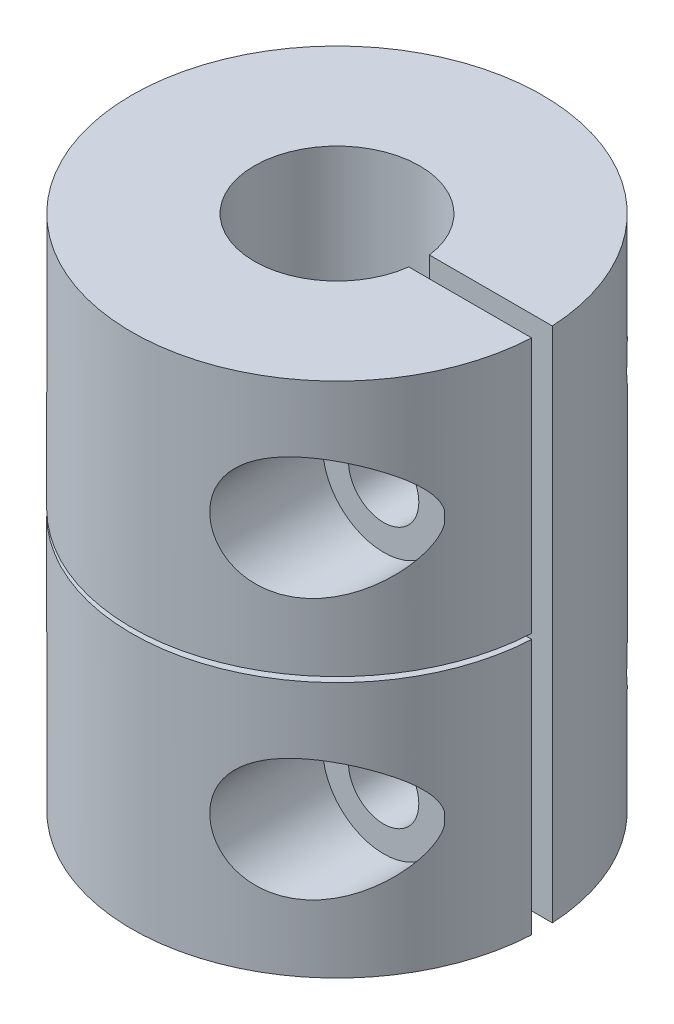
SolidWorks part; units mm, degrees
ref_plane "Front Plane" through (0, 0, 0) normal (0, 0, 1) x (1, 0, 0)
ref_plane "Top Plane" through (0, 0, 0) normal (0, 1, 0) x (1, 0, 0)
ref_plane "Right Plane" through (0, 0, 0) normal (1, 0, 0) x (0, 0, -1)
sketch "Sketch1" plane through (0, 0, 0) normal (0, 1, 0) x (1, 0, 0)
  circle A0 centre (0, 0) radius 9.925
  dimension "D1" = 19.85
extrude "Boss-Extrude1" add sketch "Sketch1" along normal mid plane 25
sketch "Sketch10" plane through (0, 0, 0) normal (0, 1, 0) x (1, 0, 0)
  line L0 (0, 0) -> (-4.9625, 8.5953)
  line L1 (0, 0) -> (9.925, 0) construction
  line L2 (0, -0.5) -> (9.9124, -0.5)
  line L3 (0, 0.5) -> (9.9124, 0.5)
  line L4 (0, 0.5) -> (9.925, 0.5) construction
  line L5 (0, -0.5) -> (9.925, -0.5) construction
  line L6 (0, -0.5) -> (0, 0)
  line L7 (0, 0.5) -> (-0.2887, 0.5)
  circle A0 centre (0, 0) radius 9.925 construction
  circle A2 centre (0, 0) radius 9.925
  circle A3 centre (0, 0) radius 9.925
  dimension "D1" = 60
  dimension "D2" = 0
  dimension "D3" = 0.5
  dimension "D4" = 0.5
extrude "Cut-Extrude5" cut sketch "Sketch10" against normal mid plane 0.25 contours L0 A3 L2 L6 region at (-1.5239, 0, 2.4216)
sketch "Sketch3" plane through (0, 12.5, 0) normal (0, 1, 0) x (1, 0, 0)
  circle A0 centre (0, 0) radius 4
  dimension "D1" = 8
extrude "Cut-Extrude1" cut sketch "Sketch3" against normal up to surface (12.625 mm away) up to face at (-0.6756, -0.125, 1.23)
sketch "Sketch4" plane through (0, -0.125, 0) normal (0, 1, 0) x (1, 0, 0)
  circle A0 centre (0, 0) radius 2.5
  dimension "D1" = 5
extrude "Cut-Extrude2" cut sketch "Sketch4" against normal through all
extrude "Cut-Extrude6" cut sketch "Sketch10<4>" against normal through all both and the other way through all contours L2 A3 L3 L7 L0 L6 region at (4.9239, 0, -0.0024)
sketch "Sketch10<4>" plane through (0, 0, 0) normal (0, 1, 0) x (1, 0, 0) same geometry as "Sketch10"
ref_plane "Plane1" through (0, 0, 9.925) normal (0, 0, 1) x (1, 0, 0)
hole_wizard "CBORE for M3 SHCS1" positions "Sketch11" profile "Sketch12" counterbore size "M3" standard "ANSI Metric" end condition up to next
sketch "Sketch11" plane through (0, 0, 9.925) normal (0, 0, 1) x (1, 0, 0)
  line L4 (6.1809, -12.5) -> (6.1809, -0.125) construction
  line L6 (2.4495, -12.5) -> (9.9124, -12.5) construction
  line L7 (2.4495, -0.125) -> (9.9124, -0.125) construction
  line L8 (0, 0) -> (9.9124, 0) construction
  line L9 (9.9124, -12.5) -> (9.9124, 12.5) construction
  point P2 (6.1809, -6.3125)
  point P37 (6.1809, 6.3125)
sketch "Sketch12" plane through (6.1809, -6.3125, 9.925) normal (1, 0, 0) x (0, -1, 0)
  line L0 (0, 0) -> (0, 9.425)
  line L1 (0, 9.425) -> (1.7, 9.425)
  line L3 (1.7, 9.425) -> (1.7, 6)
  line L4 (1.7, 6) -> (2.95, 6)
  line L5 (2.95, 6) -> (2.95, 0)
  line L7 (2.95, 0) -> (0, 0)
  line L11 (0, -6.35) -> (0, 107.95) construction
  dimension "Thru Hole Dia." = 3.4
  dimension "Thru Hole Depth" = 9.425
  dimension "C'Bore Dia." = 5.9
  dimension "C'Bore Depth" = 6
hole_wizard "M3x0.5 Tapped Hole1" positions "Sketch13" profile "Sketch14" tap size "M3x0.5" standard "ANSI Metric" end condition up to next
sketch "Sketch13" plane through (0, 0, -0.5) normal (0, 0, 1) x (1, 0, 0)
  point P0 (6.1809, 6.3125)
  point P3 (6.1809, -6.3125)
sketch "Sketch14" plane through (6.1809, 6.3125, -0.5) normal (1, 0, 0) x (0, -1, 0)
  line L0 (0, 0) -> (0, 7.2654)
  line L1 (0, 7.2654) -> (1.25, 7.2654)
  line L2 (1.25, 7.2654) -> (1.25, 0)
  line L5 (1.25, 0) -> (0, 0)
  line L11 (0, -6.35) -> (0, 107.95) construction
  dimension "Thru Tap Drill Dia." = 2.5
  dimension "Thru Tap Drill Depth" = 7.2654
cosmetic thread "Hole Thread1" parameters "D2"=3
cosmetic thread "Hole Thread2" parameters "D2"=3
